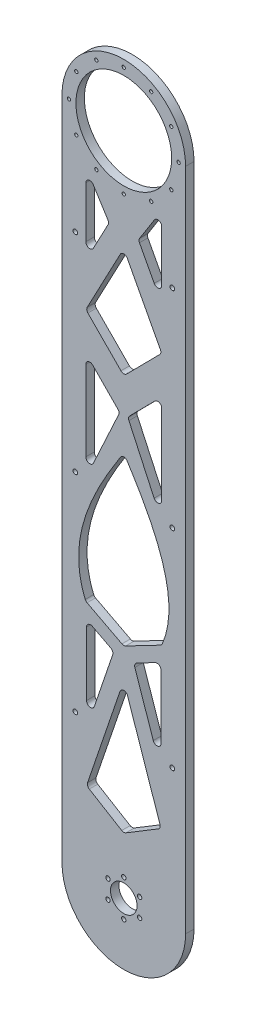
SolidWorks part; units mm, degrees
material "1060 Alloy"
ref_plane "Front Plane" through (0, 0, 0) normal (0, 0, 1) x (1, 0, 0)
ref_plane "Top Plane" through (0, 0, 0) normal (0, 1, 0) x (1, 0, 0)
ref_plane "Right Plane" through (0, 0, 0) normal (1, 0, 0) x (0, 0, -1)
sketch "Sketch2" plane through (0, 0, 0) normal (0, 0, 1) x (1, 0, 0)
  line L0 (0, 0) -> (0, 500) construction
  line L1 (-46.5, 0) -> (-46.5, 500)
  line L2 (46.5, 0) -> (46.5, 500)
  arc A0 (-46.5, 0) -> (46.5, 0) centre (0, 0) ccw
  arc A1 (46.5, 500) -> (-46.5, 500) centre (0, 500) ccw
  circle A2 centre (0, 500) radius 37.25 construction
  circle A3 centre (0, 0) radius 10
  circle A4 centre (0, 13.75) radius 1.65
  circle A5 centre (0, 0) radius 13.75 construction
  circle A6 centre (11.9078, 6.875) radius 1.65
  circle A7 centre (11.9078, -6.875) radius 1.65
  circle A8 centre (0, -13.75) radius 1.65
  circle A9 centre (-11.9078, -6.875) radius 1.65
  circle A10 centre (-11.9078, 6.875) radius 1.65
  point P3 (0, 250)
  point P27 (0, 0)
  dimension "D2" = 74.5
  dimension "D4" = 20
  dimension "D5" = 3.3
  dimension "D6" = 27.5
  dimension "D3" = 46.5
  dimension "D1" = 500
  dimension "D7" = 6
extrude "Boss-Extrude1" add sketch "Sketch2" along normal blind 6.35
sketch "Sketch4" plane through (0, 0, 6.35) normal (0, 0, 1) x (1, 0, 0)
  line L0 (0, 500) -> (0, 999.1647) construction
  line L29 (46.5, 500) -> (-46.5, 500) construction
  line L31 (28.0053, 59.376) -> (0, 42.4117)
  line L32 (0, 141.6934) -> (28.0053, 59.376)
  line L33 (-28.0053, 59.376) -> (0, 141.6934)
  line L34 (0, 42.4117) -> (-28.0053, 59.376)
  line L35 (-7.5, 156.9059) -> (-28.0053, 96.6336)
  line L36 (-28.0053, 167.5829) -> (-7.5, 156.9059)
  line L37 (-28.0053, 96.6336) -> (-28.0053, 167.5829)
  line L38 (28.0053, 167.5829) -> (7.5, 156.9059)
  line L39 (28.0053, 96.6336) -> (28.0053, 167.5829)
  line L40 (7.5, 156.9059) -> (28.0053, 96.6336)
  line L41 (0, 164.2751) -> (28.5505, 179.1412)
  line L42 (0, 164.2751) -> (-28.5505, 179.1412)
  line L43 (28.5505, 259.5868) -> (3, 314.9383)
  line L44 (28.5505, 340.7931) -> (28.5505, 259.5868)
  line L45 (3, 314.9383) -> (28.5505, 340.7931)
  line L46 (-3, 314.9383) -> (-28.5505, 340.7931)
  line L47 (-28.5505, 259.5868) -> (-3, 314.9383)
  line L48 (-28.5505, 340.7931) -> (-28.5505, 259.5868)
  line L49 (0, 423.1428) -> (-28.5505, 369.2462)
  line L50 (-28.5505, 369.2462) -> (0, 340.3557)
  line L51 (0, 340.3557) -> (28.5505, 369.2462)
  line L52 (0, 423.1428) -> (28.5505, 369.2462)
  line L53 (-28.5505, 462.0952) -> (-28.5505, 401.2902)
  line L54 (-11, 434.4215) -> (-28.5505, 462.0952)
  line L55 (-28.5505, 401.2902) -> (-11, 434.4215)
  line L56 (28.5505, 401.2902) -> (11, 434.4215)
  line L57 (28.5505, 462.0952) -> (28.5505, 401.2902)
  line L58 (11, 434.4215) -> (28.5505, 462.0952)
  arc A0 (46.5, 500) -> (-46.5, 500) centre (0, 500) ccw construction
  arc A1 (46.5, 500) -> (-46.5, 500) centre (0, 500) ccw construction
  spline S2 degree 3 poles (28.5505, 179.1412) (45.3203, 216.9857) (19.4301, 259.7903) (0, 290.0258) knots 0 0 0 0 1 1 1 1
  spline S3 degree 3 poles (-28.5505, 179.1412) (-45.3203, 216.9857) (-19.4301, 259.7903) (0, 290.0258) knots 0 0 0 0 1 1 1 1
extrude "Cut-Extrude1" cut sketch "Sketch4" against normal blind 10
fillet "Fillet3" radius 3 30 edges at (-11, 434.4215, 3.175) (-28.5505, 401.2902, 3.175) (28.5505, 401.2902, 3.175) (11, 434.4215, 3.175) (28.5505, 462.0952, 3.175) (-28.5505, 462.0952, 3.175) (0, 423.1428, 3.175) (-28.5505, 369.2462, 3.175) (28.5505, 369.2462, 3.175) (0, 340.3557, 3.175) (28.5505, 340.7931, 3.175) (-28.5505, 340.7931, 3.175) (-3, 314.9383, 3.175) (3, 314.9383, 3.175) (28.5505, 259.5868, 3.175) (-28.5505, 259.5868, 3.175) (28.5505, 179.1412, 3.175) (0, 290.0258, 3.175) (-28.5505, 179.1412, 3.175) (0, 164.2751, 3.175) (-28.0053, 96.6336, 3.175) (28.0053, 96.6336, 3.175) (7.5, 156.9059, 3.175) (-28.0053, 167.5829, 3.175) (28.0053, 167.5829, 3.175) (0, 141.6934, 3.175) (28.0053, 59.376, 3.175) (-28.0053, 59.376, 3.175) (0, 42.4117, 3.175) (-7.5, 156.9059, 3.175)
sketch "Sketch5" plane through (0, 0, 6.35) normal (0, 0, 1) x (1, 0, 0)
  line L0 (0, -46.5) -> (108.8395, -46.5) construction
  line L1 (46.5, 100) -> (-46.5, 100) construction
  line L2 (46.5, 0) -> (46.5, 500) construction
  line L3 (-46.5, 500) -> (-46.5, 0) construction
  line L4 (-46.5, 106.35) -> (46.5, 106.35) construction
  line L5 (36.5, 106.35) -> (36.5, 100) construction
  line L6 (0, 106.35) -> (0, 100) construction
  line L7 (-46.5, 256.35) -> (46.5, 256.35) construction
  line L8 (-46.5, 181.35) -> (46.5, 181.35) construction
  line L9 (-46.5, 337.7) -> (46.5, 337.7) construction
  arc A1 (-46.5, 0) -> (46.5, 0) centre (0, 0) ccw construction
  circle A2 centre (36.5, 103.175) radius 1.75
  circle A3 centre (-36.5, 103.175) radius 1.75
  circle A4 centre (36.5, 259.525) radius 1.75
  circle A5 centre (-36.5, 259.525) radius 1.75
  circle A6 centre (36.5, 415.875) radius 1.75
  circle A7 centre (-36.5, 415.875) radius 1.75
  point P18 (36.5, 103.175)
  dimension "D2" = 3.5
  dimension "D1" = 146.5
  dimension "D3" = 10
  dimension "D4" = 6.35
  dimension "D5" = 150
  dimension "D6" = 81.35
  dimension "D7" = 81.35
extrude "Cut-Extrude2" cut sketch "Sketch5" against normal through all
sketch "Sketch6" plane through (0, 0, 6.35) normal (0, 0, 1) x (1, 0, 0)
  circle A0 centre (0, 500) radius 26.5
  arc A1 (46.5, 500) -> (-46.5, 500) centre (0, 500) ccw construction
  arc A2 (46.5, 500) -> (-46.5, 500) centre (0, 500) ccw construction
  dimension "D1" = 20
extrude "Cut-Extrude3" cut sketch "Sketch6" against normal blind 10
sketch "Sketch7" plane through (0, 0, 6.35) normal (0, 0, 1) x (1, 0, 0)
  line L1 (40.0163, 523.6842) -> (44.1104, 529.9682) construction
  line L2 (23.6842, 540.0163) -> (29.9682, 544.1104) construction
  line L3 (44.1104, 529.9682) -> (29.9682, 544.1104)
  line L4 (0, 500) -> (37.0393, 537.0393) construction
  line L5 (0, 500) -> (0, 546.5) construction
  arc A0 (46.5, 500) -> (-46.5, 500) centre (0, 500) ccw construction
  arc A1 (29.9682, 544.1104) -> (16.4747, 543.4837) centre (22.4977, 559.381) cw
  arc A2 (44.1104, 529.9682) -> (43.4837, 516.4747) centre (59.381, 522.4977) ccw
  arc A3 (16.4747, 543.4837) -> (43.4837, 516.4747) centre (0, 500) cw
  dimension "D3" = 17
  dimension "D5" = 17
  dimension "D1" = 20
  dimension "D2" = 7.5
  dimension "D4" = 8
  dimension "D6" = 8
  dimension "D7" = 45
extrude "Boss-Extrude2" add sketch "Sketch7" against normal up to surface (6.35 mm away) up to face at (26.5, 500, 0)
sketch "Sketch8" plane through (287.0393, 287.0393, 0) normal (0.7071, 0.7071, 0) x (0, 0, -1)
  line L0 (0, 363.5534) -> (-6.35, 363.5534) construction
  line L1 (0, 343.5534) -> (-6.35, 343.5534) construction
  line L2 (-6.35, 343.5534) -> (-6.35, 363.5534) construction
  point P0 (-3.175, 359.5534)
  point P1 (-3.175, 347.5534)
  dimension "D1" = 4
  dimension "D2" = 4
  dimension "D3" = 3.175
hole_wizard "Tap Drill for M3x0.5 Tap1" positions "Sketch8" profile "Sketch9" hole size "M3x0.5" standard "ANSI Metric"
sketch "Sketch9" plane through (32.7967, 541.282, 3.175) normal (0, 0, 1) x (-0.7071, 0.7071, 0)
  line L0 (0, 0) -> (0, 5.7511)
  line L1 (0, 5.7511) -> (1.25, 5)
  line L2 (1.25, 5) -> (1.25, 0)
  line L5 (1.25, 0) -> (0, 0)
  line L10 (0, 5.7511) -> (-1.25, 5) construction
  line L11 (0, -6.35) -> (0, 107.95) construction
  dimension "Hole Dia." = 2.5
  dimension "Hole Depth" = 5
  dimension "Drill Angle" = 118
pattern_circular "CirPattern2" count 2 every 90 about axis through (0, 500, -3.65) along (0, 0, 1) of "Boss-Extrude2", "Tap Drill for M3x0.5 Tap1"
sketch "Sketch10" plane through (0, 0, 6.35) normal (0, 0, 1) x (1, 0, 0)
  line L0 (-43.4837, 516.4747) -> (-63.4837, 516.4747)
  line L1 (43.4837, 516.4747) -> (63.4837, 516.4747)
  arc A0 (43.4837, 516.4747) -> (-43.4837, 516.4747) centre (0, 500) ccw
  arc A1 (46.5, 500) -> (43.4837, 516.4747) centre (0, 500) ccw construction
  arc A2 (-63.4837, 516.4747) -> (63.4837, 516.4747) centre (0, 500) cw
  dimension "D1" = 19.0866
  dimension "D2" = 20
extrude "Cut-Extrude4" cut sketch "Sketch10" against normal through all
sketch "Sketch11" plane through (0, 0, 6.35) normal (0, 0, 1) x (1, 0, 0)
  circle A0 centre (0, 500) radius 36
  circle A1 centre (0, 500) radius 26.5 construction
  point P2 (11.7047, 486.431)
  dimension "D1" = 72
extrude "Cut-Extrude5" cut sketch "Sketch11" against normal through all
sketch "Sketch12" plane through (0, 0, 6.35) normal (0, 0, 1) x (1, 0, 0)
  line L0 (0, 536) -> (0, 546.5) construction
  circle A0 centre (0, 500) radius 41.25 construction
  circle A1 centre (0, 500) radius 36 construction
  arc A2 (46.5, 500) -> (-46.5, 500) centre (0, 500) ccw construction
  circle A3 centre (0, 541.25) radius 1.25
  circle A4 centre (20.625, 535.7235) radius 1.25
  circle A5 centre (35.7235, 520.625) radius 1.25
  circle A6 centre (41.25, 500) radius 1.25
  circle A7 centre (35.7235, 479.375) radius 1.25
  circle A8 centre (20.625, 464.2765) radius 1.25
  circle A9 centre (0, 458.75) radius 1.25
  circle A10 centre (-20.625, 464.2765) radius 1.25
  circle A11 centre (-35.7235, 479.375) radius 1.25
  circle A12 centre (-41.25, 500) radius 1.25
  circle A13 centre (-35.7235, 520.625) radius 1.25
  circle A14 centre (-20.625, 535.7235) radius 1.25
  point P9 (0, 541.25)
  point P36 (0, 500)
  dimension "D1" = 2.5
  dimension "D2" = 12
extrude "Cut-Extrude6" cut sketch "Sketch12" against normal through all both and the other way through all
equation "\"L1L\"=500"
equation "\"L1Thick\"=6.35"
equation "\"D1@Sketch2\"=\"L1L\""
equation "\"Harm-Drive-Outer\"=74.5"
equation "\"D2@Sketch2\"=\"Harm-Drive-Outer\""
equation "\"D1@Boss-Extrude1\"=\"L1Thick\""
